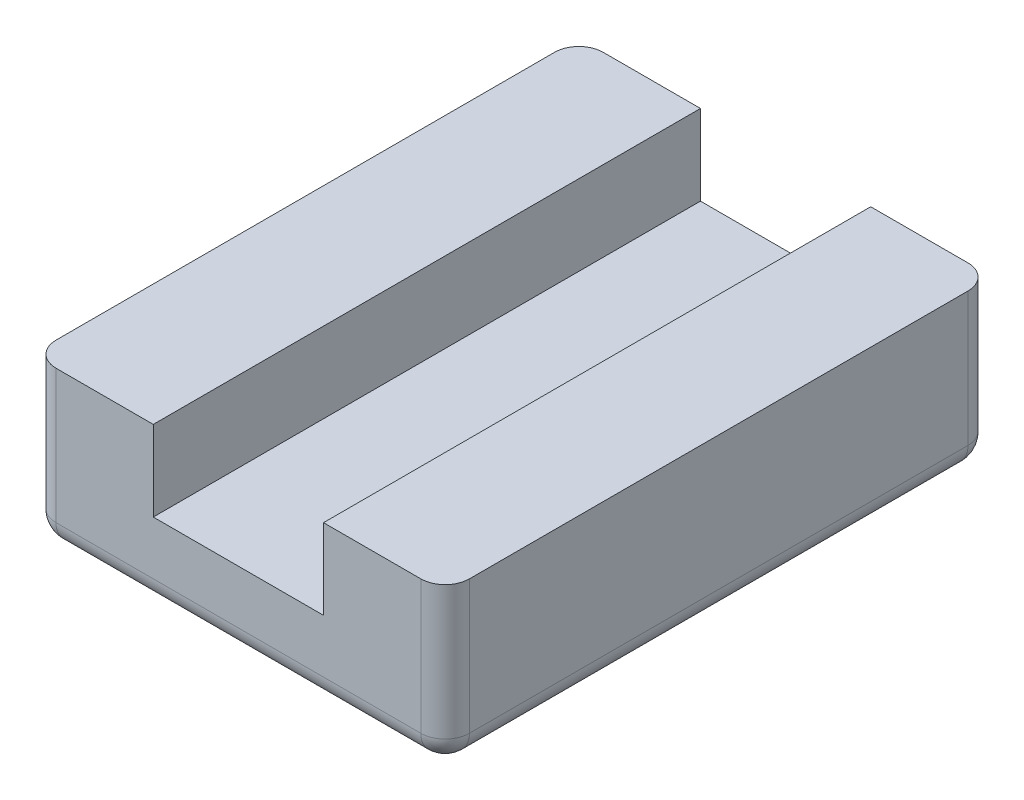
SolidWorks part; units mm, degrees
ref_plane "前视基准面" through (0, 0, 0) normal (0, 0, 1) x (1, 0, 0)
ref_plane "上视基准面" through (0, 0, 0) normal (0, 1, 0) x (1, 0, 0)
ref_plane "右视基准面" through (0, 0, 0) normal (1, 0, 0) x (0, 0, -1)
sketch "草图1" plane through (0, 0, 0) normal (0, 0, 1) x (1, 0, 0)
  line L0 (12, 0) -> (17, 0)
  line L1 (0, 0) -> (5, 0)
  line L2 (0, 0) -> (0, -6.5)
  line L3 (0, -6.5) -> (17, -6.5)
  line L4 (17, 0) -> (17, -6.5)
  line L6 (5, 0) -> (5, -3.3)
  line L7 (5, -3.3) -> (12, -3.3)
  line L8 (12, 0) -> (12, -3.3)
extrude "凸台-拉伸1" add sketch "草图1" along normal blind 22.5
fillet "圆角1" radius 1 4 edges at (0, -6.5, 11.25) (8.5, -6.5, 0) (17, -6.5, 11.25) (8.5, -6.5, 22.5)
fillet "圆角2" radius 1 8 edges at (0.2929, -6.2071, 22.2071) (16.7071, -6.2071, 22.2071) (16.7071, -6.2071, 0.2929) (0.2929, -6.2071, 0.2929) (0, -2.75, 22.5) (17, -2.75, 22.5) (17, -2.75, 0) (0, -2.75, 0)
sketch "草图2" plane through (0, -6.5, 0) normal (0, -1, 0) x (1, 0, 0)
  circle A0 centre (2.5, 7.25) radius 1
  circle A1 centre (2.5, 15.25) radius 1
  circle A2 centre (14.5, 7.25) radius 1
  circle A3 centre (14.5, 15.25) radius 1
  dimension "D1" = 2
  dimension "D2" = 2
extrude "切除-拉伸1" cut sketch "草图2" against normal blind 2.5
